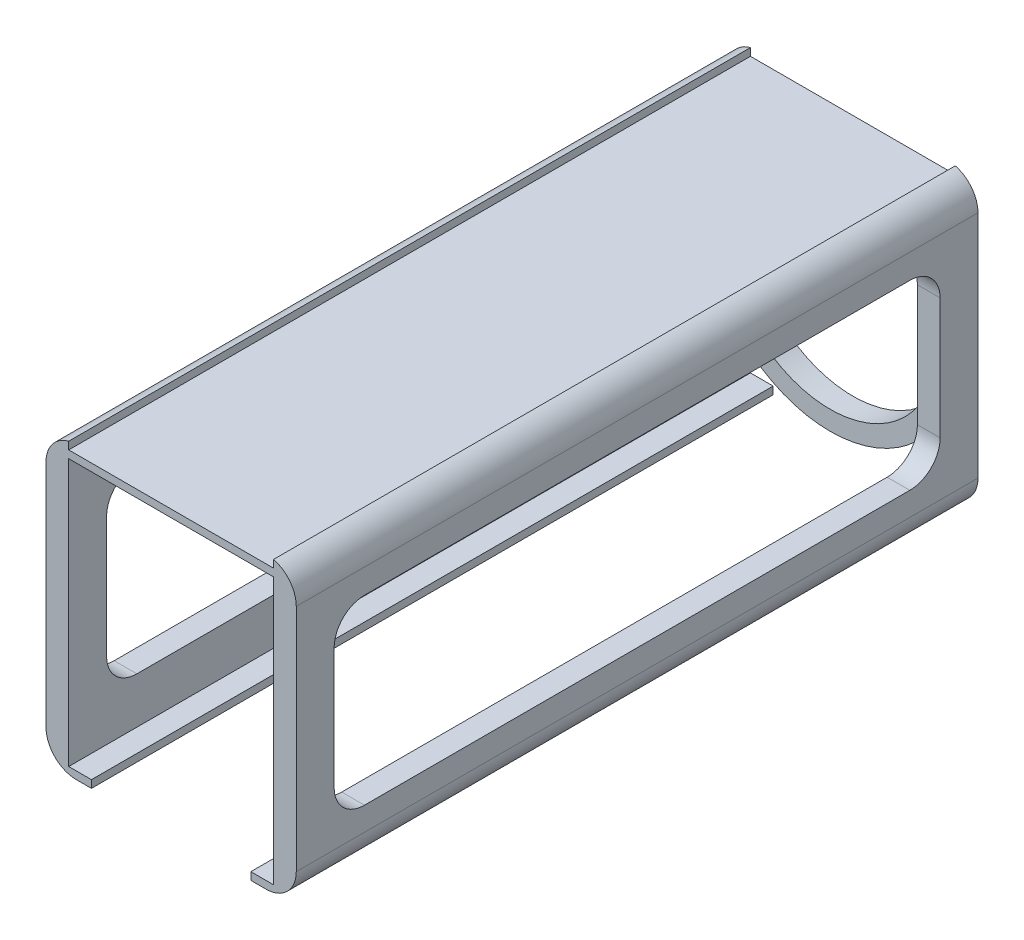
SolidWorks part; units mm, degrees
material "ABS"
ref_plane "Front Plane" through (0, 0, 0) normal (0, 0, 1) x (1, 0, 0)
ref_plane "Top Plane" through (0, 0, 0) normal (0, 1, 0) x (1, 0, 0)
ref_plane "Right Plane" through (0, 0, 0) normal (1, 0, 0) x (0, 0, -1)
sketch "Sketch1" plane through (0, 0, 0) normal (0, 1, 0) x (1, 0, 0)
  line L0 (4.7625, 142.875) -> (4.7625, 0) construction
  line L1 (0, 0) -> (9.525, 0)
  line L2 (0, 0) -> (0, 142.875)
  line L3 (0, 142.875) -> (9.525, 142.875)
  line L4 (9.525, 0) -> (9.525, 142.875)
  line L5 (52.451, 0) -> (42.926, 0)
  line L6 (52.451, 0) -> (52.451, 142.875)
  line L7 (52.451, 142.875) -> (42.926, 142.875)
  line L8 (42.926, 0) -> (42.926, 142.875)
  line L9 (47.6885, 142.875) -> (47.6885, 0) construction
  dimension "D1" = 4.7625
  dimension "D2" = 142.875
  dimension "D3" = 4.7625
  dimension "D4" = 42.926
extrude "Boss-Extrude1" add sketch "Sketch1" along normal blind 1.5875
sketch "Sketch2" plane through (0, 1.5875, 0) normal (0, 1, 0) x (1, 0, 0)
  line L0 (9.525, 142.875) -> (0, 142.875) construction
  line L1 (0, 0) -> (4.7625, 0)
  line L2 (0, 0) -> (0, 142.875)
  line L3 (0, 142.875) -> (4.7625, 142.875)
  line L4 (4.7625, 0) -> (4.7625, 142.875)
  line L5 (52.451, 142.875) -> (42.926, 142.875) construction
  line L6 (52.451, 0) -> (47.6885, 0)
  line L7 (52.451, 0) -> (52.451, 142.875)
  line L8 (52.451, 142.875) -> (47.6885, 142.875)
  line L9 (47.6885, 0) -> (47.6885, 142.875)
extrude "Boss-Extrude2" add sketch "Sketch2" along normal blind 59.055
sketch "Sketch3" plane through (0, 0, 0) normal (-1, 0, 0) x (0, 0, 1)
  line L0 (-71.4375, 60.6425) -> (-71.4375, 0) construction
  line L1 (-142.875, 60.6425) -> (0, 60.6425) construction
  line L2 (-142.875, 0) -> (0, 0) construction
  line L4 (-7.9375, 49.3712) -> (-134.9375, 49.3712)
  line L5 (-7.9375, 49.3712) -> (-7.9375, 11.2712)
  line L6 (-7.9375, 11.2712) -> (-134.9375, 11.2712)
  line L7 (-134.9375, 49.3712) -> (-134.9375, 11.2712)
  line L8 (-7.9375, 49.3712) -> (-134.9375, 11.2712) construction
  line L9 (-7.9375, 11.2712) -> (-134.9375, 49.3712) construction
  point P6 (-71.4375, 30.3212)
  dimension "D1" = 127
  dimension "D2" = 38.1
extrude "Cut-Extrude1" cut sketch "Sketch3" against normal through all
sketch "Sketch4" plane through (0, 0, -142.875) normal (0, 0, -1) x (-1, 0, 0)
  line L0 (-52.451, 30.3213) -> (0, 30.3213) construction
  line L1 (-52.451, 60.6425) -> (-52.451, 0) construction
  line L2 (0, 60.6425) -> (0, 0) construction
  circle A0 centre (-26.2255, 30.3213) radius 26.2255
  circle A1 centre (-26.2255, 30.3213) radius 22.225
  dimension "D1" = 44.45
extrude "Boss-Extrude3" add sketch "Sketch4" against normal blind 4.7625
sketch "Sketch5" plane through (0, 0, 0) normal (0, 0, 1) x (1, 0, 0)
  line L0 (0, 58.2613) -> (52.451, 58.2613) construction
  line L1 (0, 60.6425) -> (0, 0) construction
  line L2 (52.451, 60.6425) -> (52.451, 0) construction
  line L4 (48.4505, 59.055) -> (4.0005, 59.055)
  line L5 (48.4505, 59.055) -> (48.4505, 57.4675)
  line L6 (48.4505, 57.4675) -> (4.0005, 57.4675)
  line L7 (4.0005, 59.055) -> (4.0005, 57.4675)
  line L8 (48.4505, 59.055) -> (4.0005, 57.4675) construction
  line L9 (48.4505, 57.4675) -> (4.0005, 59.055) construction
  point P6 (26.2255, 58.2613)
  dimension "D1" = 56.6738
  dimension "D2" = 0.7937
  dimension "D3" = 44.45
fillet "Fillet1" radius 6.35 4 edges at (52.451, 0, -71.4375) (0, 0, -71.4375) (0, 60.6425, -71.4375) (52.451, 60.6425, -71.4375)
fillet "Fillet4" radius 6.35 8 edges at (2.3813, 11.2712, -7.9375) (2.3813, 49.3712, -7.9375) (2.3813, 49.3712, -134.9375) (2.3813, 11.2712, -134.9375) (50.0698, 11.2712, -7.9375) (50.0698, 11.2712, -134.9375) (50.0698, 49.3712, -134.9375) (50.0698, 49.3712, -7.9375)
extrude "Boss-Extrude4" add sketch "Sketch5" against normal blind 142.875
